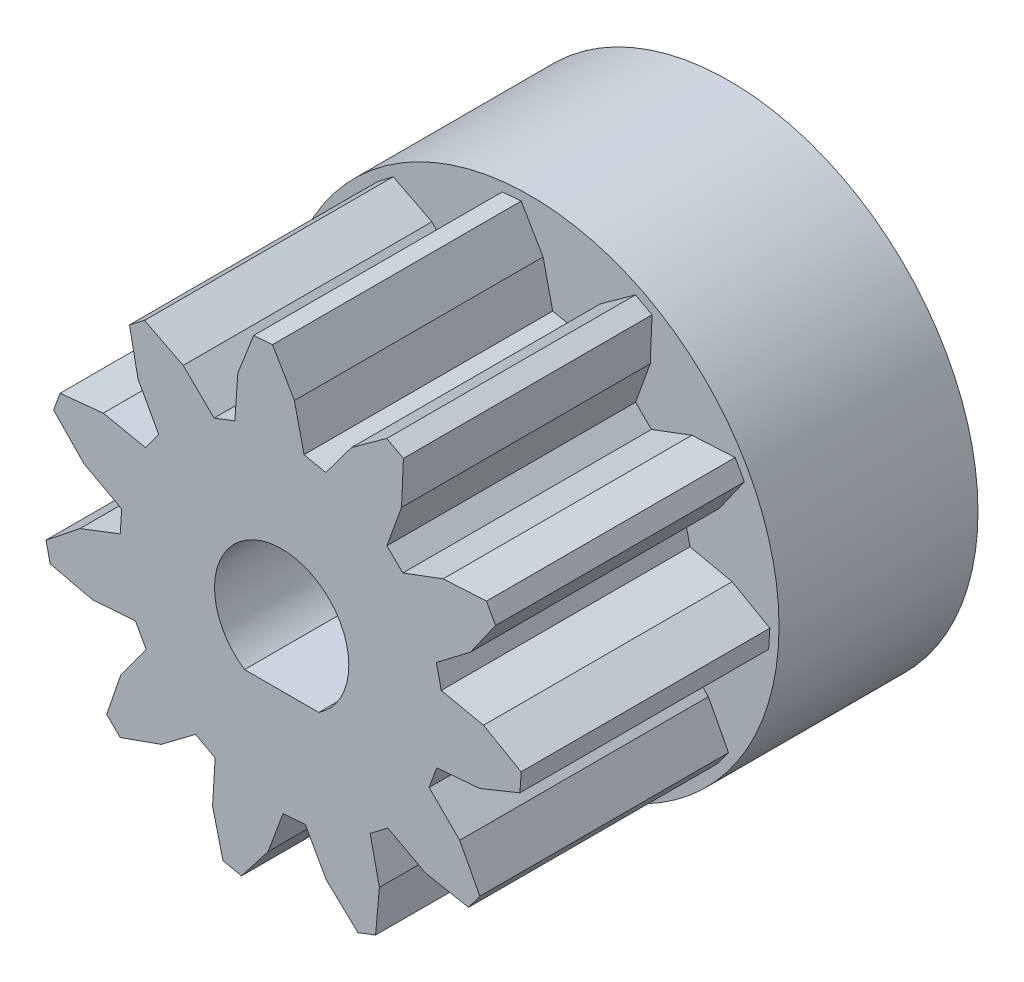
SolidWorks part; units mm, degrees
ref_plane "Front Plane" through (0, 0, 0) normal (0, 0, 1) x (1, 0, 0)
ref_plane "Top Plane" through (0, 0, 0) normal (0, 1, 0) x (1, 0, 0)
ref_plane "Right Plane" through (0, 0, 0) normal (1, 0, 0) x (0, 0, -1)
sketch "Sketch1" plane through (0, 0, 0) normal (0, 0, 1) x (1, 0, 0)
  line L0 (16.2784, 26.4067) -> (15.4438, 27.928)
  line L1 (15.4438, 27.928) -> (15.1018, 29.6384)
  line L2 (15.1018, 29.6384) -> (15.7072, 30.0975)
  line L3 (15.7072, 30.0975) -> (17.261, 29.3062)
  line L4 (17.261, 29.3062) -> (18.5017, 28.0929)
  line L5 (18.5017, 28.0929) -> (19.3385, 28.4109)
  line L6 (19.3385, 28.4109) -> (19.4589, 30.142)
  line L7 (19.4589, 30.142) -> (20.0959, 31.7657)
  line L8 (20.0959, 31.7657) -> (20.8533, 31.8246)
  line L9 (20.8533, 31.8246) -> (21.7327, 30.3189)
  line L10 (21.7327, 30.3189) -> (22.1205, 28.6274)
  line L11 (22.1205, 28.6274) -> (22.9964, 28.4426)
  line L12 (22.9964, 28.4426) -> (24.0335, 29.8337)
  line L13 (24.0335, 29.8337) -> (25.4473, 30.8553)
  line L14 (25.4473, 30.8553) -> (26.1163, 30.4954)
  line L15 (26.1163, 30.4954) -> (26.0421, 28.7532)
  line L16 (26.0421, 28.7532) -> (25.4538, 27.1206)
  line L17 (25.4538, 27.1206) -> (26.0907, 26.4916)
  line L18 (26.0907, 26.4916) -> (27.7153, 27.1012)
  line L19 (27.7153, 27.1012) -> (29.457, 27.1963)
  line L20 (29.457, 27.1963) -> (29.8252, 26.5318)
  line L21 (29.8252, 26.5318) -> (28.8209, 25.1063)
  line L22 (28.8209, 25.1063) -> (27.4433, 24.0509)
  line L23 (27.4433, 24.0509) -> (27.6391, 23.1774)
  line L24 (27.6391, 23.1774) -> (29.3353, 22.8119)
  line L25 (29.3353, 22.8119) -> (30.8519, 21.9503)
  line L26 (30.8519, 21.9503) -> (30.8024, 21.1922)
  line L27 (30.8024, 21.1922) -> (29.1869, 20.536)
  line L28 (29.1869, 20.536) -> (27.4574, 20.3929)
  line L29 (27.4574, 20.3929) -> (27.1498, 19.5523)
  line L30 (27.1498, 19.5523) -> (28.3792, 18.3277)
  line L31 (28.3792, 18.3277) -> (29.1892, 16.783)
  line L32 (29.1892, 16.783) -> (28.7377, 16.1719)
  line L33 (28.7377, 16.1719) -> (27.0239, 16.4934)
  line L34 (27.0239, 16.4934) -> (25.4916, 17.308)
  line L35 (25.4916, 17.308) -> (24.7783, 16.7671)
  line L36 (24.7783, 16.7671) -> (25.1505, 15.0723)
  line L37 (25.1505, 15.0723) -> (24.9968, 13.3348)
  line L38 (24.9968, 13.3348) -> (24.2866, 13.0649)
  line L39 (24.2866, 13.0649) -> (23.0186, 14.2619)
  line L40 (23.0186, 14.2619) -> (22.17, 15.7756)
  line L41 (22.17, 15.7756) -> (21.2775, 15.7062)
  line L42 (21.2775, 15.7062) -> (20.6744, 14.0792)
  line L44 (19.6057, 12.7006) -> (20.6744, 14.0792)
  line L45 (19.6057, 12.7006) -> (18.8623, 12.8575)
  line L46 (18.8623, 12.8575) -> (18.4428, 14.55)
  line L47 (18.4428, 14.55) -> (18.5472, 16.2822)
  line L48 (18.5472, 16.2822) -> (17.7589, 16.7063)
  line L49 (17.7589, 16.7063) -> (16.3718, 15.6637)
  line L50 (16.3718, 15.6637) -> (14.7276, 15.0818)
  line L51 (14.7276, 15.0818) -> (14.187, 15.6156)
  line L52 (14.187, 15.6156) -> (14.7491, 17.2663)
  line L53 (14.7491, 17.2663) -> (15.7735, 18.6671)
  line L54 (15.7735, 18.6671) -> (15.3396, 19.4501)
  line L55 (15.3396, 19.4501) -> (13.609, 19.3228)
  line L56 (13.609, 19.3228) -> (11.9111, 19.7223)
  line L57 (11.9111, 19.7223) -> (11.745, 20.4636)
  line L58 (11.745, 20.4636) -> (13.1103, 21.5484)
  line L59 (13.1103, 21.5484) -> (14.7294, 22.1729)
  line L60 (14.7294, 22.1729) -> (14.7877, 23.0662)
  line L61 (14.7877, 23.0662) -> (13.2631, 23.8948)
  line L62 (13.2631, 23.8948) -> (12.0507, 25.1488)
  line L63 (12.0507, 25.1488) -> (12.3117, 25.8622)
  line L64 (12.3117, 25.8622) -> (14.0467, 26.0367)
  line L65 (14.0467, 26.0367) -> (15.7464, 25.6867)
  line L66 (15.7464, 25.6867) -> (16.2784, 26.4067)
  line L67 (19.7289, 19.9479) -> (22.7138, 19.9479)
  arc A0 (22.7138, 19.9479) -> (19.7289, 19.9479) centre (21.2214, 22.1979) ccw
extrude "Boss-Extrude3" add sketch "Sketch1" along normal blind 10
sketch "Sketch3" plane through (0, 0, 0) normal (0, 0, -1) x (-1, 0, 0)
  line L12 (-19.7289, 19.9479) -> (-22.7138, 19.9479) construction
  line L53 (-19.7289, 19.9479) -> (-22.7138, 19.9479)
  arc A1 (-19.7289, 19.9479) -> (-22.7138, 19.9479) centre (-21.2214, 22.1979) ccw construction
  arc A2 (-19.7289, 19.9479) -> (-22.7138, 19.9479) centre (-21.2214, 22.1979) ccw
  circle A3 centre (-21.2214, 22.1979) radius 10
extrude "Boss-Extrude4" add sketch "Sketch3" along normal blind 8
sketch "Sketch7" plane through (0, 19.9479, 0) normal (0, 1, 0) x (1, 0, 0)
  circle A0 centre (21.2214, 4.6) radius 1.7
extrude "Cut-Extrude2" cut sketch "Sketch7" against normal through all and the other way blind 2
sketch "Sketch8" plane through (0, 0, -8) normal (0, 0, -1) x (-1, 0, 0)
  line L0 (-21.2214, 12.1979) -> (-21.2214, 20.6572) construction
  line L1 (-21.2214, 12.1979) -> (-21.2214, 16.1979) construction
  line L7 (-24.2214, 15.6979) -> (-24.2214, 18.6979)
  line L9 (-18.2214, 18.6979) -> (-24.2214, 18.6979)
  line L10 (-18.2214, 15.6979) -> (-18.2214, 18.6979)
  line L11 (-24.2214, 15.6979) -> (-18.2214, 15.6979)
extrude "Cut-Extrude3" cut sketch "Sketch8" against normal blind 6.8
